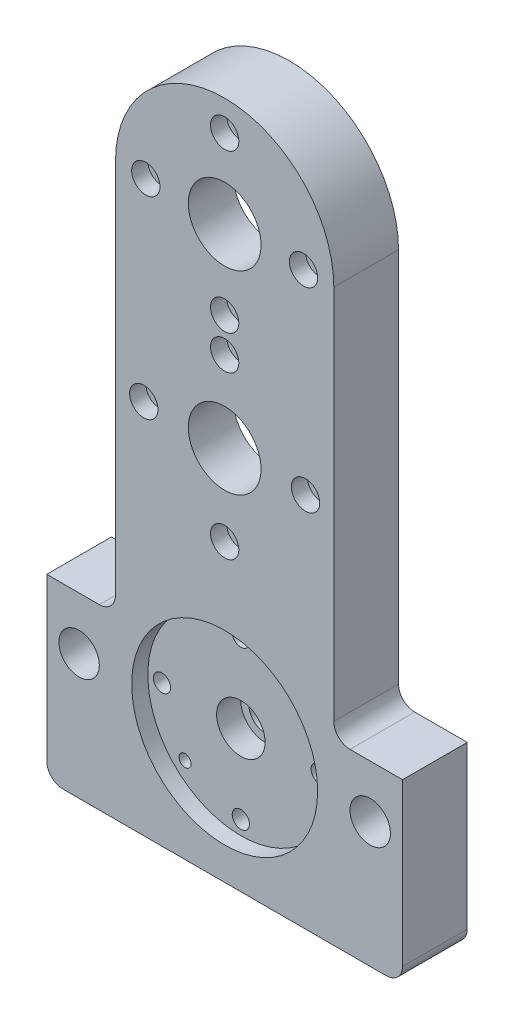
SolidWorks part; units mm, degrees
note: '?' marks a value the reader was unsure of.
material "6061 Alloy"
ref_plane "Front" through (0, 0, 0) normal (0, 0, 1) x (1, 0, 0)
ref_plane "Top" through (0, 0, 0) normal (0, 1, 0) x (1, 0, 0)
ref_plane "Right" through (0, 0, 0) normal (1, 0, 0) x (0, 0, -1)
ref_axis "Axis" through (0, 0, -80.9) along (0, 0, 1)?
sketch "Bolt circle" plane through (0, 0, 0) normal (0, 0, 1) x (1, 0, 0)
  line L0 (0, 36.5125) -> (0, 25.4) construction
  line L1 (-42.8625, 76.2) -> (-42.8625, -77.7875)
  line L2 (0, 101.6) -> (0, 112.7125) construction
  line L3 (42.8625, 76.2) -> (42.8625, -77.7875)
  line L7 (42.8625, -77.7875) -> (69.85, -77.7875)
  line L12 (-42.8625, -77.7875) -> (-69.85, -77.7875)
  line L30 (69.85, -77.7875) -> (69.85, -147.6375)
  line L31 (69.85, -147.6375) -> (-69.85, -147.6375)
  line L34 (-69.85, -77.7875) -> (-69.85, -147.6375)
  line L35 (0, 0) -> (0, -147.6375) construction
  circle A0 centre (0, 0) radius 36.5125 construction
  circle A1 centre (0, 0) radius 25.4 construction
  circle A2 centre (0, 0) radius 30.9562 construction
  arc A3 (-42.8625, 76.2) -> (42.8625, 76.2) centre (0, 76.2) cw
  circle A4 centre (0, 76.2) radius 14.2748
  circle A5 centre (0, 76.2) radius 36.5125 construction
  circle A6 centre (0, 76.2) radius 25.4 construction
  circle A7 centre (0, 0) radius 14.2748
  circle A8 centre (0, -98.425) radius 36.5125 construction
  circle A9 centre (0, -98.425) radius 6.35
  circle A10 centre (0, 76.2) radius 30.9562 construction
  point P0 (0, -36.5125)
  point P7 (0, 30.9562)
  point P9 (0, -134.9375)
  point P20 (0, 107.1562)
  dimension "D1" = 73.025
  dimension "D2" = 50.8
  dimension "D3" = 69.85
  dimension "D12" = 139.7
  dimension "D5" = 26.9875
  dimension "D13" = 28.5496
  dimension "D18" = 12.7
  dimension "D6" = 76.2
  dimension "D8" = 73.025
  dimension "D9" = 28.5496
  dimension "D10" = 50.8
  dimension "D4" = 98.425
  dimension "D7" = 85.725
  dimension "D17" = 12.7
extrude "Base" add sketch "Bolt circle" along normal mid plane 25.4
hole_wizard "Structure tube connection counterbore" positions "Sketch15" profile "Sketch14" counterbore size "1/4" standard "Ansi Inch" end condition through all
sketch "Sketch15" plane through (0, 0, -12.7) normal (0, 0, -1) x (-1, 0, 0)
  circle A0 centre (0, -98.425) radius 30.9563 construction
  point P1 (0, -67.4688)
  dimension "D1" = 61.9125
sketch "Sketch14" plane through (0, -67.4688, -12.7) normal (1, 0, 0) x (0, 1, 0)
  line L0 (0, 0) -> (0, 25.4)
  line L1 (0, 25.4) -> (3.3782, 25.4)
  line L3 (3.3782, 25.4) -> (3.3782, 6.35)
  line L4 (3.3782, 6.35) -> (5.5562, 6.35)
  line L5 (5.5562, 6.35) -> (5.5562, 0)
  line L7 (5.5562, 0) -> (0, 0)
  line L11 (0, -6.35) -> (0, 107.95) construction
  dimension "Thru Hole Dia." = 6.7564
  dimension "Thru Hole Depth" = 25.4
  dimension "C'Bore Dia." = 11.1125
  dimension "C'Bore Depth" = 6.35
pattern_circular "Structure tube connection counterbore pattern" count 4 over 360 about axis through (0, -98.425, 0) along (0, 0, 1) of "Structure tube connection counterbore"
hole_wizard "Spindle connection counterbore" positions "Sketch11" profile "Sketch10" counterbore size "1/4" standard "Ansi Inch" end condition through all
sketch "Sketch11" plane through (0, 0, 12.7) normal (0, 0, 1) x (1, 0, 0)
  circle A0 centre (0, 0) radius 31.75 construction
  point P0 (0, 31.75)
  dimension "D1" = 63.5
sketch "Sketch10" plane through (0, 31.75, 12.7) normal (1, 0, 0) x (0, -1, 0)
  line L0 (0, 0) -> (0, 25.4)
  line L1 (0, 25.4) -> (3.3782, 25.4)
  line L3 (3.3782, 25.4) -> (3.3782, 6.35)
  line L4 (3.3782, 6.35) -> (5.5562, 6.35)
  line L5 (5.5562, 6.35) -> (5.5562, 0)
  line L7 (5.5562, 0) -> (0, 0)
  line L11 (0, -6.35) -> (0, 107.95) construction
  dimension "Thru Hole Dia." = 6.7564
  dimension "Thru Hole Depth" = 25.4
  dimension "C'Bore Dia." = 11.1125
  dimension "C'Bore Depth" = 6.35
pattern_circular "Spindle connection counterbore pattern" count 4 over 360 about axis through (0, 0, 0) along (0, 0, 1) of "Spindle connection counterbore"
sketch "Sketch16" plane through (0, 0, 12.7) normal (0, 0, 1) x (1, 0, 0)
  circle A0 centre (0, -98.425) radius 36.5125
  dimension "D1" = 73.025
extrude "Structure tube mounting pocket" cut sketch "Sketch16" against normal blind 6.35
sketch "Sketch17" plane through (0, 0, -12.7) normal (0, 0, -1) x (-1, 0, 0)
  circle A0 centre (0, 0) radius 36.5125
  circle A1 centre (0, -98.425) radius 36.5125 construction
  dimension "D1" = 73.025
extrude "Spindle mounting pocket" cut sketch "Sketch17" against normal blind 7.62
sketch "Sketch18" plane through (0, 0, 6.35) normal (0, 0, 1) x (1, 0, 0)
  circle A0 centre (0, -98.425) radius 9.525
  dimension "D1" = 19.05
extrude "Lead screw through hole" cut sketch "Sketch18" against normal blind 9.525
sketch "Sketch20" plane through (0, 0, 12.7) normal (0, 0, 1) x (1, 0, 0)
  line L1 (57.15, -98.425) -> (-57.15, -98.425) construction
  circle A0 centre (57.15, -98.425) radius 7.9375
  circle A1 centre (-57.15, -98.425) radius 7.9375
  dimension "D2" = 114.3
  dimension "D3" = 15.875
extrude "Rail mounting pilot_holes" cut sketch "Sketch20" against normal through all
sketch "Sketch27" plane through (0, 0, 6.35) normal (0, 0, 1) x (1, 0, 0)
  line L0 (20.6813, -74.3354) -> (19.6028, -75.5003)
  line L1 (24.176, -77.571) -> (23.0974, -78.7359)
  line L2 (21.8894, -76.5356) -> (-21.8894, -120.3144) construction
  line L3 (20.1421, -74.9178) -> (23.6367, -78.1534) construction
  line L4 (50, 0) -> (-50, 0) construction
  circle A0 centre (-21.8894, -120.3144) radius 2.3813
  arc A1 (24.176, -77.571) -> (20.6813, -74.3354) centre (22.4286, -75.9532) ccw
  arc A2 (23.0974, -78.7359) -> (19.6028, -75.5003) centre (21.3501, -77.1181) cw
  circle A3 centre (21.8894, -76.5356) radius 2.3813 construction
  circle A4 centre (0, -98.425) radius 30.9563 construction
  point P10 (20.1421, -74.9178)
  dimension "D2" = 45
  dimension "D3" = 4.7625
  dimension "D1" = 1.5875
extrude "Alignment_features" cut sketch "Sketch27" against normal blind 6.35
fillet "Generic_rounding_fillet" radius 6.35 4 edges at (42.8625, -77.7875, 0) (-42.8625, -77.7875, 0) (-69.85, -147.6375, 0) (69.85, -147.6375, 0)
sketch "Sketch21" plane through (0, -147.6375, 0) normal (0, -1, 0) x (1, 0, 0)
  line L0 (69.85, 0) -> (-69.85, 0) construction
  line L1 (69.85, 12.7) -> (69.85, -12.7) construction
  line L2 (-69.85, 12.7) -> (-69.85, -12.7) construction
  line L3 (0, -12.7) -> (0, 12.7) construction
  line L4 (-63.5, -12.7) -> (63.5, -12.7) construction
  line L5 (-63.5, 12.7) -> (63.5, 12.7) construction
  circle A0 centre (57.15, 0) radius 4.7625
  circle A1 centre (-57.15, 0) radius 4.7625
  dimension "D1" = 9.525
  dimension "D2" = 114.3
extrude "Point_mount_bores" [suppressed] cut sketch "Sketch21" against normal blind 6.35
sketch "Sketch22" plane through (0, 0, 12.7) normal (0, 0, 1) x (1, 0, 0)
  line L0 (69.85, -77.7875) -> (49.2125, -77.7875) construction
  line L1 (56.7531, -77.7875) -> (57.5469, -77.7875)
  line L2 (56.7531, -77.7875) -> (56.7531, -111.125)
  line L3 (57.15, -111.125) -> (57.15, -98.425) construction
  line L4 (57.5469, -77.7875) -> (57.5469, -111.125)
  line L5 (0, -147.6375) -> (0, 119.0625) construction
  line L6 (-63.5, -147.6375) -> (63.5, -147.6375) construction
  line L7 (-57.15, -111.125) -> (-57.15, -98.425) construction
  line L8 (-57.5469, -77.7875) -> (-57.5469, -111.125)
  line L9 (-56.7531, -77.7875) -> (-56.7531, -111.125)
  line L10 (-56.7531, -77.7875) -> (-57.5469, -77.7875)
  arc A0 (56.7531, -111.125) -> (57.5469, -111.125) centre (57.15, -111.125) ccw
  arc A2 (-56.7531, -111.125) -> (-57.5469, -111.125) centre (-57.15, -111.125) cw
  arc A3 (42.8625, 76.2) -> (-42.8625, 76.2) centre (0, 76.2) ccw construction
  dimension "D1" = 0.7937
  dimension "D2" = 12.7
extrude "Flexure_clamp_slits" [suppressed] cut sketch "Sketch22" against normal through all
hole_wizard "Flexure_clamp_counterbore" [suppressed] positions "Sketch24" profile "Sketch23" counterbore size "1/4" standard "Ansi Inch"
sketch "Sketch24" plane through (69.85, 0, 0) normal (1, 0, 0) x (0, 0, -1)
  line L0 (0, 50) -> (0, -50) construction
  line L1 (-12.7, -77.7875) -> (12.7, -77.7875) construction
  point P0 (0, -85.725)
  dimension "D1" = 7.9375
sketch "Sketch23" plane through (69.85, -85.725, 0) normal (0, 1, 0) x (0, 0, -1)
  line L0 (0, 0) -> (0, 12.3031)
  line L1 (0, 12.3031) -> (3.3782, 12.3031)
  line L3 (3.3782, 12.3031) -> (3.3782, 6.35)
  line L4 (3.3782, 6.35) -> (5.5562, 6.35)
  line L5 (5.5562, 6.35) -> (5.5562, 0)
  line L7 (5.5562, 0) -> (0, 0)
  line L11 (0, -6.35) -> (0, 107.95) construction
  dimension "Thru Hole Dia." = 6.7564
  dimension "Thru Hole Depth" = 12.3031
  dimension "C'Bore Dia." = 11.1125
  dimension "C'Bore Depth" = 6.35
hole_wizard "Flexure_clamp_threads" [suppressed] positions "Sketch26" profile "Sketch25" tap size "1/4-20" standard "Ansi Inch"
sketch "Sketch26" [suppressed] plane through (56.7531, 0, 0) normal (1, 0, 0) x (0, 0, -1)
  point P1 (0, -85.725)
sketch "Sketch25" plane through (56.7531, -85.725, 0) normal (0, 1, 0) x (0, 0, -1)
  line L0 (0, 0) -> (0, 18.0438)
  line L1 (0, 18.0438) -> (2.5527, 16.51)
  line L2 (2.5527, 16.51) -> (2.5527, 0)
  line L5 (2.5527, 0) -> (0, 0)
  line L10 (0, 18.0438) -> (-2.5527, 16.51) construction
  line L11 (0, -6.35) -> (0, 107.95) construction
  dimension "Tap Drill Dia." = 5.1054
  dimension "Tap Drill Depth" = 16.51
  dimension "Drill Angle" = 118
cosmetic thread "Hole Thread2" [suppressed] parameters "D1"=12.7, "D2"=6.35
mirror "Flexure_clamp_fastener_holes" [suppressed] about plane through (0, 0, 0) normal (1, 0, 0)
hole_wizard "wood_spindle_CBORE" positions "Sketch28" profile "Sketch29" counterbore size "1/4" standard "ANSI Inch" end condition through all
sketch "Sketch28" plane through (0, 0, 12.7) normal (0, 0, 1) x (1, 0, 0)
  point P0 (0, 107.1562)
sketch "Sketch29" plane through (0, 107.1562, 12.7) normal (1, 0, 0) x (0, -1, 0)
  line L0 (0, 0) -> (0, 25.4)
  line L1 (0, 25.4) -> (3.3782, 25.4)
  line L3 (3.3782, 25.4) -> (3.3782, 6.35)
  line L4 (3.3782, 6.35) -> (5.5562, 6.35)
  line L5 (5.5562, 6.35) -> (5.5562, 0)
  line L7 (5.5562, 0) -> (0, 0)
  line L11 (0, -6.35) -> (0, 107.95) construction
  dimension "Thru Hole Dia." = 6.7564
  dimension "Thru Hole Depth" = 25.4
  dimension "C'Bore Dia." = 11.1125
  dimension "C'Bore Depth" = 6.35
pattern_circular "CirPattern1" count 4 over 360 about axis through (0, 76.2, 0) along (0, 0, 1) of "wood_spindle_CBORE"
sketch "Sketch30" plane through (0, 0, -12.7) normal (0, 0, -1) x (-1, 0, 0)
  circle A0 centre (0, 76.2) radius 36.5125
  dimension "D1" = 73.025
extrude "Cut-Extrude1" cut sketch "Sketch30" against normal blind 7.62
